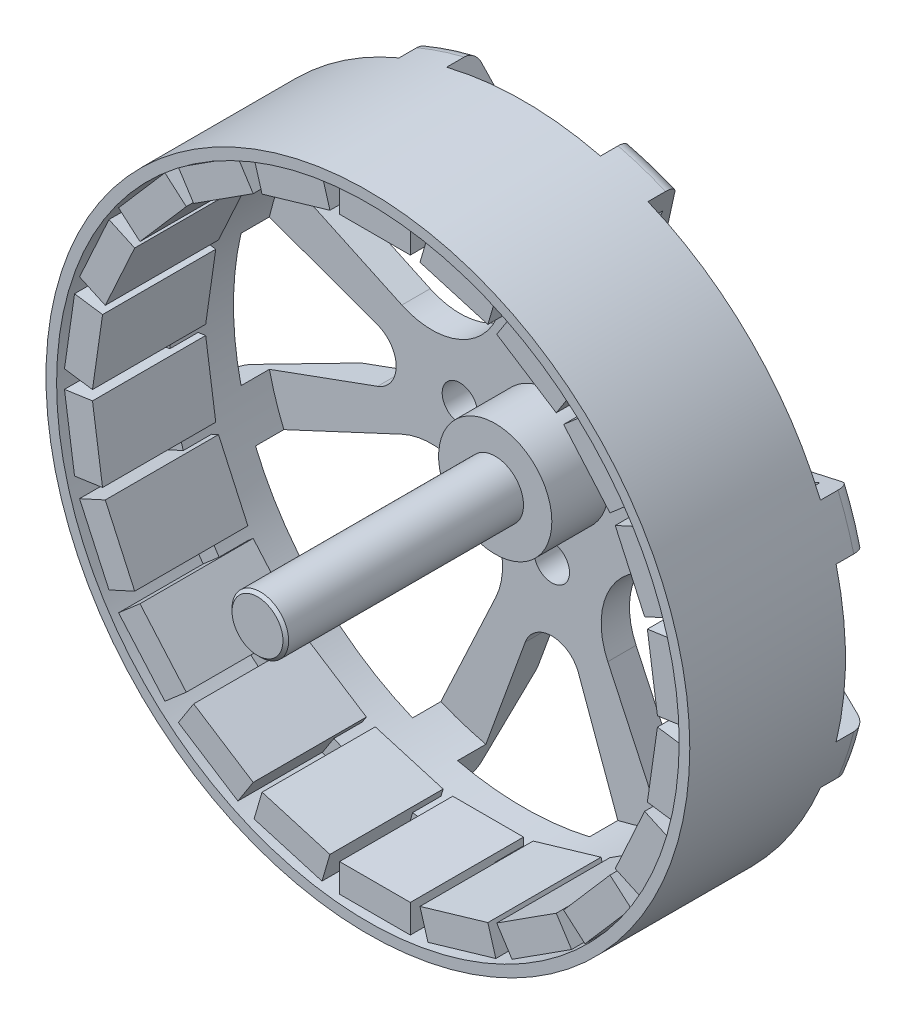
SolidWorks part; units mm, degrees
note: '?' marks a value the reader was unsure of.
ref_plane "Спереди" through (0, 0, 0) normal (0, 0, 1) x (1, 0, 0)
ref_plane "Сверху" through (0, 0, 0) normal (0, 1, 0) x (1, 0, 0)
ref_plane "Справа" through (0, 0, 0) normal (1, 0, 0) x (0, 0, -1)
sketch "Эскиз1" plane through (0, 0, 0) normal (0, 0, 1) x (1, 0, 0)
  circle A0 centre (0, 0) radius 22.75
  dimension "D1" = 45.5
extrude "Бобышка-Вытянуть1" add sketch "Эскиз1" along normal blind 15
sketch "Эскиз2" plane through (0, 0, 15) normal (0, 0, 1) x (1, 0, 0)
  circle A0 centre (0, 0) radius 22
  dimension "D1" = 44
extrude "Вырез-Вытянуть1" cut sketch "Эскиз2" against normal blind 6.5
sketch "Эскиз3" plane through (0, 0, 8.5) normal (0, 0, 1) x (1, 0, 0)
  circle A0 centre (0, 0) radius 20.5
  dimension "D1" = 41
extrude "Вырез-Вытянуть2" cut sketch "Эскиз3" against normal offset from surface (6.5 mm away) 2 up to face at (22.75, 0, 0)
sketch "Эскиз4" plane through (0, 0, 2) normal (0, 0, 1) x (1, 0, 0)
  circle A0 centre (0, 0) radius 4
  dimension "D1" = 8
extrude "Бобышка-Вытянуть2" add sketch "Эскиз4" along normal blind 4
sketch "Эскиз12" plane through (0, 0, 0) normal (0, 0, -1) x (-1, 0, 0)
  circle A0 centre (0, 0) radius 2
  dimension "D1" = 4
extrude "Вырез-Вытянуть6" cut sketch "Эскиз12" against normal up to next
sketch "Эскиз5" plane through (0, 0, 0) normal (0, 0, -1) x (-1, 0, 0)
  circle A0 centre (0, 0) radius 2
  dimension "D1" = 4
extrude "Бобышка-Вытянуть3" add sketch "Эскиз5" against normal blind 22.8 separate body
chamfer "Фаска2" distance 0.2 angle 45 2 edges at (-2, 0, 0) (-2, 0, 22.8)
chamfer "Фаска3" distance 7 distance2 2 1 edges at (22.75, 0, 0)
sketch "Эскиз6" plane through (0, 0, 0) normal (0, 0, -1) x (-1, 0, 0)
  line L0 (0, 12.486) -> (0, -12.7441) construction
  line L1 (-12.1957, 0) -> (12.3892, 0) construction
  circle A0 centre (0, 0) radius 6.5 construction
  dimension "D1" = 13
fillet "Скругление1" radius 1 2 edges at (15.75, 0, 0) (22.75, 0, 2)
hole_wizard "Отверстие обработанное метчиком M3x0.51" positions "Эскиз8" profile "Эскиз7" tap size "M3x0.5" standard "Ansi Metric" end condition up to next
sketch "Эскиз8" plane through (0, 0, 0) normal (0, 0, -1) x (-1, 0, 0)
  line L0 (0, 12.486) -> (0, -12.7441) construction
  line L1 (-12.1957, 0) -> (12.3892, 0) construction
  circle A0 centre (0, 0) radius 6.5 construction
  point P0 (0, 6.5)
  point P6 (0, -6.5)
  point P8 (6.5, 0)
  point P12 (-6.5, 0)
sketch "Эскиз7" plane through (0, 6.5, 0) normal (1, 0, 0) x (0, 1, 0)
  line L0 (0, 0) -> (0, 2.001)
  line L1 (0, 2.001) -> (1.25, 2.001)
  line L2 (1.25, 2.001) -> (1.25, 0)
  line L5 (1.25, 0) -> (0, 0)
  line L11 (0, -6.35) -> (0, 107.95) construction
  dimension "Диаметр проходного сверла" = 2.5
  dimension "Глубина проходного сверла" = 2.001
cosmetic thread "Отверстие резьбы1" parameters "D2"=3
cosmetic thread "Отверстие резьбы2" parameters "D2"=3
cosmetic thread "Отверстие резьбы3" parameters "D2"=3
cosmetic thread "Отверстие резьбы4" parameters "D2"=3
sketch "Эскиз9" plane through (0, 0, 0) normal (0, 0, -1) x (-1, 0, 0)
  line L0 (-28.0049, 0) -> (26.2626, 0) construction
  line L1 (21.2425, 21.2425) -> (-21.2425, -21.2425) construction
  line L2 (3.9537, 10.5984) -> (8.7953, 20.9811)
  line L3 (-17.5401, 17.5401) -> (17.5401, -17.5401) construction
  line L4 (10.5984, 3.9537) -> (20.9811, 8.7953)
  line L5 (10.5984, -3.9537) -> (20.9811, -8.7953)
  line L6 (3.9537, -10.5984) -> (8.7953, -20.9811)
  line L7 (-3.9537, -10.5984) -> (-8.7953, -20.9811)
  line L8 (-10.5984, -3.9537) -> (-20.9811, -8.7953)
  line L9 (-10.5984, 3.9537) -> (-20.9811, 8.7953)
  line L10 (-3.9537, 10.5984) -> (-8.7953, 20.9811)
  arc A0 (3.9537, 10.5984) -> (10.5984, 3.9537) centre (8.4853, 8.4853) ccw
  circle A1 centre (0, 0) radius 22.75 construction
  arc A2 (8.7953, 20.9811) -> (20.9811, 8.7953) centre (0, 0) cw
  arc A3 (20.9811, -8.7953) -> (8.7953, -20.9811) centre (0, 0) cw
  arc A4 (10.5984, -3.9537) -> (3.9537, -10.5984) centre (8.4853, -8.4853) ccw
  arc A5 (-8.7953, -20.9811) -> (-20.9811, -8.7953) centre (0, 0) cw
  arc A6 (-3.9537, -10.5984) -> (-10.5984, -3.9537) centre (-8.4853, -8.4853) ccw
  arc A7 (-20.9811, 8.7953) -> (-8.7953, 20.9811) centre (0, 0) cw
  arc A8 (-10.5984, 3.9537) -> (-3.9537, 10.5984) centre (-8.4853, 8.4853) ccw
  point P33 (0, 0)
  dimension "D5" = 5
  dimension "D1" = 45
  dimension "D2" = 20
  dimension "D3" = 20
  dimension "D4" = 12
  dimension "D6" = 4
extrude "Вырез-Вытянуть3" cut sketch "Эскиз9" against normal blind 4
sketch "Эскиз10" plane through (0, 0, 0) normal (0, 0, -1) x (-1, 0, 0)
  line L0 (0, 24.2945) -> (0, -25.9077) construction
  line L1 (-1.8794, 12.316) -> (-5.4371, 22.0907)
  line L2 (1.8794, 12.316) -> (5.4371, 22.0907)
  line L3 (12.316, 1.8794) -> (22.0907, 5.4371)
  line L4 (12.316, -1.8794) -> (22.0907, -5.4371)
  line L5 (1.8794, -12.316) -> (5.4371, -22.0907)
  line L6 (-1.8794, -12.316) -> (-5.4371, -22.0907)
  line L7 (-12.316, -1.8794) -> (-22.0907, -5.4371)
  line L8 (-12.316, 1.8794) -> (-22.0907, 5.4371)
  arc A0 (-1.8794, 12.316) -> (1.8794, 12.316) centre (0, 13) ccw
  arc A1 (8.7953, 20.9811) -> (-8.7953, 20.9811) centre (0, 0) ccw construction
  arc A2 (-5.4371, 22.0907) -> (5.4371, 22.0907) centre (0, 0) cw
  arc A3 (22.0907, 5.4371) -> (22.0907, -5.4371) centre (0, 0) cw
  arc A4 (12.316, 1.8794) -> (12.316, -1.8794) centre (13, 0) ccw
  arc A5 (5.4371, -22.0907) -> (-5.4371, -22.0907) centre (0, 0) cw
  arc A6 (1.8794, -12.316) -> (-1.8794, -12.316) centre (0, -13) ccw
  arc A7 (-22.0907, -5.4371) -> (-22.0907, 5.4371) centre (0, 0) cw
  arc A8 (-12.316, -1.8794) -> (-12.316, 1.8794) centre (-13, 0) ccw
  point P30 (0, 0)
  dimension "D3" = 2
  dimension "D4" = 13
  dimension "D1" = 20
  dimension "D2" = 20
  dimension "D5" = 4
extrude "Вырез-Вытянуть4" cut sketch "Эскиз10" against normal blind 4
ref_plane "Плоскость1" through (0, 0, 14.5) normal (0, 0, 1) x (1, 0, 0)
sketch "Эскиз13" plane through (0, 0, 14.5) normal (0, 0, 1) x (1, 0, 0)
  line L0 (0, 24.0307) -> (0, 6.5) construction
  line L2 (-2.5, 21.8087) -> (2.5, 21.8087)
  line L3 (-2.5, 21.8087) -> (-2.5, 19.8087)
  line L4 (-2.5, 19.8087) -> (2.5, 19.8087)
  line L5 (2.5, 21.8087) -> (2.5, 19.8087)
  line L6 (-2.5, 21.8087) -> (2.5, 19.8087) construction
  line L7 (-2.5, 19.8087) -> (2.5, 21.8087) construction
  point P3 (0, 20.8087)
  dimension "D1" = 5
  dimension "D2" = 2
ref_axis "Ось1" through (0, 0, 22.6) along (0, 0, -1)?
extrude "Бобышка-Вытянуть6" add sketch "Эскиз13" against normal blind 8
pattern_circular "Круговой массив5" count 22 over 360 about axis through (0, 0, 0) along (0, 0, 1) of "Бобышка-Вытянуть6"
